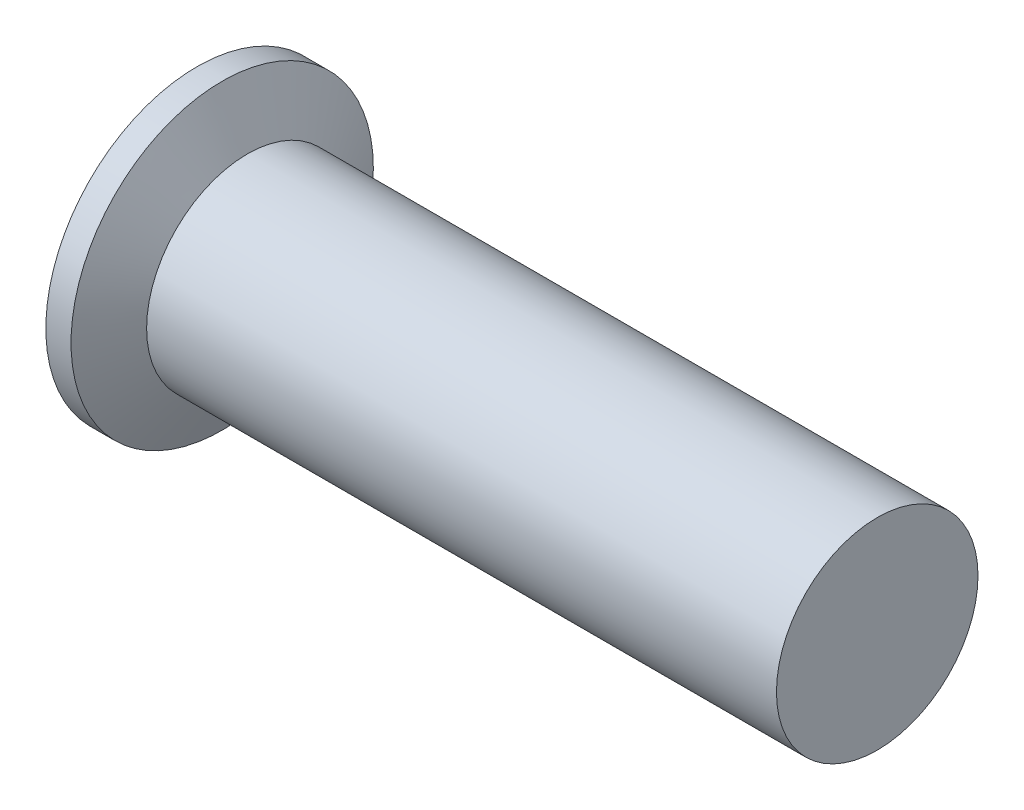
SolidWorks part; units mm, degrees
material "AISI 1015 Steel, Cold Drawn (SS)"
ref_plane "Front Plane" through (0, 0, 0) normal (1, 0, 0) x (0, 1, 0)
ref_plane "Top Plane" through (0, 0, 0) normal (0, 0, 1) x (0, 1, 0)
ref_plane "Right Plane" through (0, 0, 0) normal (0, 1, 0) x (-1, 0, 0)
sketch "Sketch1" plane through (0, 0, 0) normal (1, 0, 0) x (0, 1, 0)
  circle A0 centre (0, 0) radius 3
  circle A1 centre (0, 0) radius 2
  dimension "D1" = 6
  dimension "D2" = 4
extrude "Boss-Extrude1" add sketch "Sketch1" along normal blind 1 contours A0
extrude "Boss-Extrude2" add sketch "Sketch1<4>" along normal blind 13.5 contours A1
sketch "Sketch1<4>" plane through (0, 0, 0) normal (1, 0, 0) x (0, 1, 0) same geometry as "Sketch1"
sketch "Sketch2" plane through (0, 0, 0) normal (0, 1, 0) x (-1, 0, 0)
  line L0 (-0.6837, 0) -> (1.059, 0) construction
  line L1 (0, 3) -> (-1, 3) construction
  line L2 (-0.5, 3) -> (-1, 2)
  line L3 (-1, 2) -> (-1, 3)
  line L4 (-1, 3) -> (-1, -3) construction
  line L5 (-1, 3) -> (-0.5, 3)
revolve "Cut-Revolve1" cut sketch "Sketch2" angle 360 about L0
